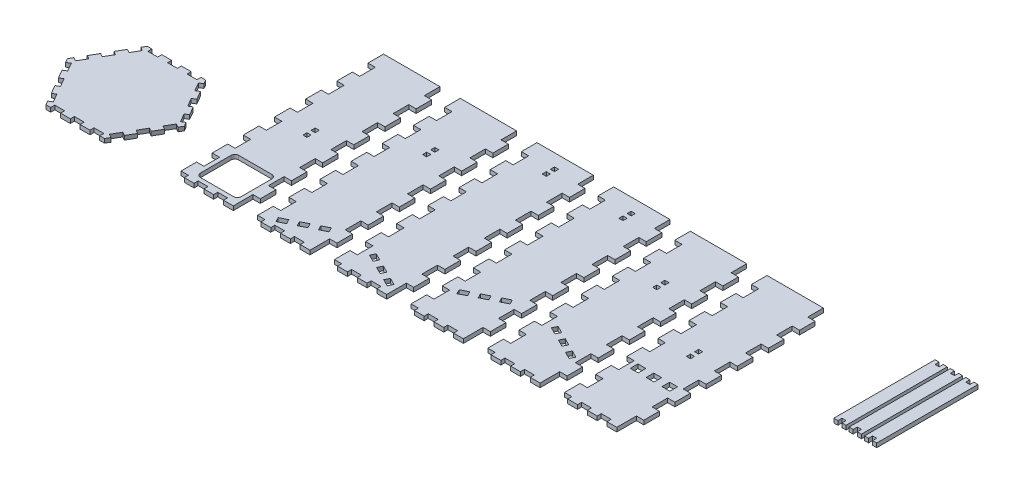
SolidWorks part; units mm, degrees
ref_plane "Front Plane" through (0, 0, 0) normal (0, 0, 1) x (1, 0, 0)
ref_plane "Top Plane" through (0, 0, 0) normal (0, 1, 0) x (1, 0, 0)
ref_plane "Right Plane" through (0, 0, 0) normal (1, 0, 0) x (0, 0, -1)
sketch "Sketch1" plane through (0, 0, 0) normal (0, 1, 0) x (1, 0, 0)
  line L0 (-22.87, -39.612) -> (-19.175, -39.612)
  line L13 (-19.175, -39.612) -> (-19.175, -36.412)
  line L14 (-19.175, -36.412) -> (-11.505, -36.412)
  line L15 (-11.505, -36.412) -> (-11.505, -39.612)
  line L16 (-11.505, -39.612) -> (-3.835, -39.612)
  line L17 (-3.835, -39.612) -> (-3.835, -36.412)
  line L18 (-3.835, -36.412) -> (3.835, -36.412)
  line L19 (3.835, -36.412) -> (3.835, -39.612)
  line L21 (-45.74, 0) -> (-43.8925, -3.2)
  line L22 (3.835, -39.612) -> (11.505, -39.612)
  line L23 (11.505, -39.612) -> (11.505, -36.412)
  line L24 (11.505, -36.412) -> (19.175, -36.412)
  line L25 (19.175, -36.412) -> (19.175, -39.612)
  line L26 (19.175, -39.612) -> (22.87, -39.612)
  line L27 (22.87, -39.612) -> (24.7175, -36.412)
  line L28 (45.74, 0) -> (22.87, 39.612) construction
  line L29 (24.7175, -36.412) -> (21.9462, -34.812)
  line L30 (21.9462, -34.812) -> (25.7812, -28.1696)
  line L31 (25.7812, -28.1696) -> (28.5525, -29.7696)
  line L32 (28.5525, -29.7696) -> (32.3875, -23.1272)
  line L33 (32.3875, -23.1272) -> (29.6162, -21.5272)
  line L34 (29.6162, -21.5272) -> (33.4512, -14.8848)
  line L35 (33.4512, -14.8848) -> (36.2225, -16.4848)
  line L36 (36.2225, -16.4848) -> (40.0575, -9.8424)
  line L37 (40.0575, -9.8424) -> (37.2862, -8.2424)
  line L38 (37.2862, -8.2424) -> (41.1212, -1.6)
  line L39 (41.1212, -1.6) -> (43.8925, -3.2)
  line L40 (43.8925, -3.2) -> (45.74, 0)
  line L41 (45.74, 0) -> (43.8925, 3.2)
  line L42 (22.87, 39.612) -> (-22.87, 39.612) construction
  line L43 (-22.87, 39.612) -> (-45.74, 0) construction
  line L44 (43.8925, 3.2) -> (41.1212, 1.6)
  line L45 (41.1212, 1.6) -> (37.2862, 8.2424)
  line L46 (37.2862, 8.2424) -> (40.0575, 9.8424)
  line L47 (40.0575, 9.8424) -> (36.2225, 16.4848)
  line L48 (36.2225, 16.4848) -> (33.4512, 14.8848)
  line L49 (33.4512, 14.8848) -> (29.6162, 21.5272)
  line L50 (29.6162, 21.5272) -> (32.3875, 23.1272)
  line L51 (32.3875, 23.1272) -> (28.5525, 29.7696)
  line L52 (28.5525, 29.7696) -> (25.7812, 28.1696)
  line L53 (25.7812, 28.1696) -> (21.9462, 34.812)
  line L54 (21.9462, 34.812) -> (24.7175, 36.412)
  line L55 (24.7175, 36.412) -> (22.87, 39.612)
  line L56 (22.87, 39.612) -> (19.175, 39.612)
  line L57 (-45.74, 0) -> (-22.87, -39.612) construction
  line L58 (-22.87, -39.612) -> (22.87, -39.612) construction
  line L59 (19.175, 39.612) -> (19.175, 36.412)
  line L60 (19.175, 36.412) -> (11.505, 36.412)
  line L61 (11.505, 36.412) -> (11.505, 39.612)
  line L62 (11.505, 39.612) -> (3.835, 39.612)
  line L63 (3.835, 39.612) -> (3.835, 36.412)
  line L64 (3.835, 36.412) -> (-3.835, 36.412)
  line L65 (-3.835, 36.412) -> (-3.835, 39.612)
  line L66 (-3.835, 39.612) -> (-11.505, 39.612)
  line L67 (-11.505, 39.612) -> (-11.505, 36.412)
  line L68 (-11.505, 36.412) -> (-19.175, 36.412)
  line L69 (-19.175, 36.412) -> (-19.175, 39.612)
  line L70 (-19.175, 39.612) -> (-22.87, 39.612)
  line L71 (-22.87, 39.612) -> (-24.7175, 36.412)
  line L72 (22.87, -39.612) -> (45.74, 0) construction
  line L73 (-43.8925, -3.2) -> (-41.1212, -1.6)
  line L74 (-24.7175, 36.412) -> (-21.9462, 34.812)
  line L75 (-21.9462, 34.812) -> (-25.7812, 28.1696)
  line L76 (-25.7812, 28.1696) -> (-28.5525, 29.7696)
  line L77 (-28.5525, 29.7696) -> (-32.3875, 23.1272)
  line L78 (-32.3875, 23.1272) -> (-29.6162, 21.5272)
  line L79 (-29.6162, 21.5272) -> (-33.4512, 14.8848)
  line L80 (-33.4512, 14.8848) -> (-36.2225, 16.4848)
  line L81 (-36.2225, 16.4848) -> (-40.0575, 9.8424)
  line L82 (-40.0575, 9.8424) -> (-37.2862, 8.2424)
  line L83 (-37.2862, 8.2424) -> (-41.1212, 1.6)
  line L84 (-41.1212, 1.6) -> (-43.8925, 3.2)
  line L85 (-43.8925, 3.2) -> (-45.74, 0)
  line L86 (-41.1212, -1.6) -> (-37.2862, -8.2424)
  line L87 (-37.2862, -8.2424) -> (-40.0575, -9.8424)
  line L88 (-40.0575, -9.8424) -> (-36.2225, -16.4848)
  line L89 (-36.2225, -16.4848) -> (-33.4512, -14.8848)
  line L90 (-33.4512, -14.8848) -> (-29.6162, -21.5272)
  line L91 (-29.6162, -21.5272) -> (-32.3875, -23.1272)
  line L92 (-32.3875, -23.1272) -> (-28.5525, -29.7696)
  line L93 (-28.5525, -29.7696) -> (-25.7812, -28.1696)
  line L94 (-25.7812, -28.1696) -> (-21.9462, -34.812)
  line L95 (-21.9462, -34.812) -> (-24.7175, -36.412)
  line L96 (-24.7175, -36.412) -> (-22.87, -39.612)
  line L97 (-21.9462, -34.812) -> (-19.175, -39.612) construction
  line L102 (19.175, -36.412) -> (24.7175, -36.412) construction
  line L103 (-19.175, -36.412) -> (-24.7175, -36.412) construction
  line L104 (80.5528, -34.8794) -> (88.2227, -34.8794)
  line L105 (88.2227, -34.8794) -> (88.2227, -31.6794)
  line L106 (88.2227, -31.6794) -> (95.8927, -31.6794)
  line L107 (95.8927, -31.6794) -> (95.8927, -34.8794)
  line L108 (95.8927, -34.8794) -> (103.5627, -34.8794)
  line L109 (103.5627, -34.8794) -> (103.5627, -31.6794)
  line L110 (103.5627, -31.6794) -> (111.2327, -31.6794)
  line L111 (111.2327, -31.6794) -> (111.2327, -34.8794)
  line L112 (111.2327, -34.8794) -> (118.9027, -34.8794)
  line L113 (80.5528, -34.8794) -> (80.5528, -31.6794)
  line L114 (80.5528, -31.6794) -> (74.8102, -31.6794)
  line L115 (74.8102, -31.6794) -> (74.8102, -19.4911)
  line L116 (74.8102, -19.4911) -> (80.5528, -19.4911)
  line L117 (80.5528, -19.4911) -> (80.5528, -7.3028)
  line L118 (80.5528, -7.3028) -> (74.8102, -7.3028)
  line L121 (118.9027, -7.3028) -> (124.6452, -7.3028)
  line L122 (124.6452, -7.3028) -> (124.6452, -19.4911)
  line L123 (124.6452, -19.4911) -> (118.9027, -19.4911)
  line L124 (118.9027, -19.4911) -> (118.9027, -34.8794)
  line L126 (21.9462, -34.812) -> (19.175, -39.612) construction
  line L250 (140.5528, -34.8794) -> (148.2227, -34.8794)
  line L265 (148.2227, -34.8794) -> (148.2227, -31.6794)
  line L266 (148.2227, -31.6794) -> (155.8927, -31.6794)
  line L267 (155.8927, -31.6794) -> (155.8927, -34.8794)
  line L268 (155.8927, -34.8794) -> (163.5627, -34.8794)
  line L269 (163.5627, -34.8794) -> (163.5627, -31.6794)
  line L270 (74.8102, -7.3028) -> (74.8102, 4.8855)
  line L271 (74.8102, 4.8855) -> (80.5528, 4.8855)
  line L272 (80.5528, 4.8855) -> (80.5528, 17.0739)
  line L273 (80.5528, 17.0739) -> (74.8102, 17.0739)
  line L274 (74.8102, 17.0739) -> (74.8102, 29.2622)
  line L275 (74.8102, 29.2622) -> (80.5528, 29.2622)
  line L276 (80.5528, 29.2622) -> (80.5528, 41.4505)
  line L277 (80.5528, 41.4505) -> (74.8102, 41.4505)
  line L278 (74.8102, 41.4505) -> (74.8102, 53.6388)
  line L279 (74.8102, 53.6388) -> (80.5528, 53.6388)
  line L280 (80.5528, 53.6388) -> (80.5528, 65.8271)
  line L281 (80.5528, 65.8271) -> (74.8102, 65.8271)
  line L282 (74.8102, 65.8271) -> (74.8102, 78.0154)
  line L283 (74.8102, 78.0154) -> (80.5528, 78.0154)
  line L284 (80.5528, 78.0154) -> (80.5528, 90.2037)
  line L285 (80.5528, 90.2037) -> (74.8102, 90.2037)
  line L286 (74.8102, 90.2037) -> (74.8102, 102.392)
  line L287 (74.8102, 102.392) -> (80.5528, 102.392)
  line L288 (80.5528, 102.392) -> (80.5528, 114.5803)
  line L289 (80.5528, 114.5803) -> (74.8102, 114.5803)
  line L290 (74.8102, 114.5803) -> (74.8102, 126.7686)
  line L291 (118.9027, -7.3028) -> (118.9027, 4.8855)
  line L292 (118.9027, 4.8855) -> (124.6452, 4.8855)
  line L293 (124.6452, 4.8855) -> (124.6452, 17.0739)
  line L294 (124.6452, 17.0739) -> (118.9027, 17.0739)
  line L295 (118.9027, 17.0739) -> (118.9027, 29.2622)
  line L296 (118.9027, 29.2622) -> (124.6452, 29.2622)
  line L297 (124.6452, 29.2622) -> (124.6452, 41.4505)
  line L298 (124.6452, 41.4505) -> (118.9027, 41.4505)
  line L299 (118.9027, 41.4505) -> (118.9027, 53.6388)
  line L300 (118.9027, 53.6388) -> (124.6452, 53.6388)
  line L301 (124.6452, 53.6388) -> (124.6452, 65.8271)
  line L302 (124.6452, 65.8271) -> (118.9027, 65.8271)
  line L303 (118.9027, 65.8271) -> (118.9027, 78.0154)
  line L304 (118.9027, 78.0154) -> (124.6452, 78.0154)
  line L305 (124.6452, 78.0154) -> (124.6452, 90.2037)
  line L306 (124.6452, 90.2037) -> (118.9027, 90.2037)
  line L307 (118.9027, 90.2037) -> (118.9027, 102.392)
  line L308 (118.9027, 102.392) -> (124.6452, 102.392)
  line L309 (124.6452, 102.392) -> (124.6452, 114.5803)
  line L310 (124.6452, 114.5803) -> (118.9027, 114.5803)
  line L311 (118.9027, 114.5803) -> (118.9027, 126.7686)
  line L312 (163.5627, -31.6794) -> (171.2327, -31.6794)
  line L313 (171.2327, -31.6794) -> (171.2327, -34.8794)
  line L314 (171.2327, -34.8794) -> (178.9027, -34.8794)
  line L315 (140.5528, -34.8794) -> (140.5528, -31.6794)
  line L316 (140.5528, -31.6794) -> (134.8102, -31.6794)
  line L317 (134.8102, -31.6794) -> (134.8102, -19.4911)
  line L318 (134.8102, -19.4911) -> (140.5528, -19.4911)
  line L319 (140.5528, -19.4911) -> (140.5528, -7.3028)
  line L320 (140.5528, -7.3028) -> (134.8102, -7.3028)
  line L322 (178.9027, -7.3028) -> (184.6452, -7.3028)
  line L323 (184.6452, -7.3028) -> (184.6452, -19.4911)
  line L324 (184.6452, -19.4911) -> (178.9027, -19.4911)
  line L325 (178.9027, -19.4911) -> (178.9027, -34.8794)
  line L326 (134.8102, -7.3028) -> (134.8102, 4.8855)
  line L327 (134.8102, 4.8855) -> (140.5528, 4.8855)
  line L328 (140.5528, 4.8855) -> (140.5528, 17.0739)
  line L329 (140.5528, 17.0739) -> (134.8102, 17.0739)
  line L330 (134.8102, 17.0739) -> (134.8102, 29.2622)
  line L331 (134.8102, 29.2622) -> (140.5528, 29.2622)
  line L332 (140.5528, 29.2622) -> (140.5528, 41.4505)
  line L333 (140.5528, 41.4505) -> (134.8102, 41.4505)
  line L334 (134.8102, 41.4505) -> (134.8102, 53.6388)
  line L335 (134.8102, 53.6388) -> (140.5528, 53.6388)
  line L336 (140.5528, 53.6388) -> (140.5528, 65.8271)
  line L337 (140.5528, 65.8271) -> (134.8102, 65.8271)
  line L338 (134.8102, 65.8271) -> (134.8102, 78.0154)
  line L339 (134.8102, 78.0154) -> (140.5528, 78.0154)
  line L340 (140.5528, 78.0154) -> (140.5528, 90.2037)
  line L341 (140.5528, 90.2037) -> (134.8102, 90.2037)
  line L342 (134.8102, 90.2037) -> (134.8102, 102.392)
  line L343 (134.8102, 102.392) -> (140.5528, 102.392)
  line L344 (140.5528, 102.392) -> (140.5528, 114.5803)
  line L345 (140.5528, 114.5803) -> (134.8102, 114.5803)
  line L346 (134.8102, 114.5803) -> (134.8102, 126.7686)
  line L347 (178.9027, -7.3028) -> (178.9027, 4.8855)
  line L348 (178.9027, 4.8855) -> (184.6452, 4.8855)
  line L349 (184.6452, 4.8855) -> (184.6452, 17.0739)
  line L350 (184.6452, 17.0739) -> (178.9027, 17.0739)
  line L351 (178.9027, 17.0739) -> (178.9027, 29.2622)
  line L352 (178.9027, 29.2622) -> (184.6452, 29.2622)
  line L353 (184.6452, 29.2622) -> (184.6452, 41.4505)
  line L354 (184.6452, 41.4505) -> (178.9027, 41.4505)
  line L355 (178.9027, 41.4505) -> (178.9027, 53.6388)
  line L356 (178.9027, 53.6388) -> (184.6452, 53.6388)
  line L357 (184.6452, 53.6388) -> (184.6452, 65.8271)
  line L358 (184.6452, 65.8271) -> (178.9027, 65.8271)
  line L359 (178.9027, 65.8271) -> (178.9027, 78.0154)
  line L360 (178.9027, 78.0154) -> (184.6452, 78.0154)
  line L361 (184.6452, 78.0154) -> (184.6452, 90.2037)
  line L362 (184.6452, 90.2037) -> (178.9027, 90.2037)
  line L363 (178.9027, 90.2037) -> (178.9027, 102.392)
  line L364 (178.9027, 102.392) -> (184.6452, 102.392)
  line L365 (184.6452, 102.392) -> (184.6452, 114.5803)
  line L366 (184.6452, 114.5803) -> (178.9027, 114.5803)
  line L367 (178.9027, 114.5803) -> (178.9027, 126.7686)
  line L369 (200.5528, -34.8794) -> (208.2227, -34.8794)
  line L370 (208.2227, -34.8794) -> (208.2227, -31.6794)
  line L371 (208.2227, -31.6794) -> (215.8927, -31.6794)
  line L372 (215.8927, -31.6794) -> (215.8927, -34.8794)
  line L373 (215.8927, -34.8794) -> (223.5627, -34.8794)
  line L374 (223.5627, -34.8794) -> (223.5627, -31.6794)
  line L375 (223.5627, -31.6794) -> (231.2327, -31.6794)
  line L376 (231.2327, -31.6794) -> (231.2327, -34.8794)
  line L377 (231.2327, -34.8794) -> (238.9027, -34.8794)
  line L378 (200.5528, -34.8794) -> (200.5528, -31.6794)
  line L379 (200.5528, -31.6794) -> (194.8102, -31.6794)
  line L380 (194.8102, -31.6794) -> (194.8102, -19.4911)
  line L381 (194.8102, -19.4911) -> (200.5528, -19.4911)
  line L382 (200.5528, -19.4911) -> (200.5528, -7.3028)
  line L383 (200.5528, -7.3028) -> (194.8102, -7.3028)
  line L385 (238.9027, -7.3028) -> (244.6452, -7.3028)
  line L386 (244.6452, -7.3028) -> (244.6452, -19.4911)
  line L387 (244.6452, -19.4911) -> (238.9027, -19.4911)
  line L388 (238.9027, -19.4911) -> (238.9027, -34.8794)
  line L389 (194.8102, -7.3028) -> (194.8102, 4.8855)
  line L390 (194.8102, 4.8855) -> (200.5528, 4.8855)
  line L391 (200.5528, 4.8855) -> (200.5528, 17.0739)
  line L392 (200.5528, 17.0739) -> (194.8102, 17.0739)
  line L393 (194.8102, 17.0739) -> (194.8102, 29.2622)
  line L394 (194.8102, 29.2622) -> (200.5528, 29.2622)
  line L395 (200.5528, 29.2622) -> (200.5528, 41.4505)
  line L396 (200.5528, 41.4505) -> (194.8102, 41.4505)
  line L397 (194.8102, 41.4505) -> (194.8102, 53.6388)
  line L398 (194.8102, 53.6388) -> (200.5528, 53.6388)
  line L399 (200.5528, 53.6388) -> (200.5528, 65.8271)
  line L400 (200.5528, 65.8271) -> (194.8102, 65.8271)
  line L401 (194.8102, 65.8271) -> (194.8102, 78.0154)
  line L402 (194.8102, 78.0154) -> (200.5528, 78.0154)
  line L403 (200.5528, 78.0154) -> (200.5528, 90.2037)
  line L404 (200.5528, 90.2037) -> (194.8102, 90.2037)
  line L405 (194.8102, 90.2037) -> (194.8102, 102.392)
  line L406 (194.8102, 102.392) -> (200.5528, 102.392)
  line L407 (200.5528, 102.392) -> (200.5528, 114.5803)
  line L408 (200.5528, 114.5803) -> (194.8102, 114.5803)
  line L409 (194.8102, 114.5803) -> (194.8102, 126.7686)
  line L410 (238.9027, -7.3028) -> (238.9027, 4.8855)
  line L411 (238.9027, 4.8855) -> (244.6452, 4.8855)
  line L412 (244.6452, 4.8855) -> (244.6452, 17.0739)
  line L413 (244.6452, 17.0739) -> (238.9027, 17.0739)
  line L414 (238.9027, 17.0739) -> (238.9027, 29.2622)
  line L415 (238.9027, 29.2622) -> (244.6452, 29.2622)
  line L416 (244.6452, 29.2622) -> (244.6452, 41.4505)
  line L417 (244.6452, 41.4505) -> (238.9027, 41.4505)
  line L418 (238.9027, 41.4505) -> (238.9027, 53.6388)
  line L419 (238.9027, 53.6388) -> (244.6452, 53.6388)
  line L420 (244.6452, 53.6388) -> (244.6452, 65.8271)
  line L421 (244.6452, 65.8271) -> (238.9027, 65.8271)
  line L422 (238.9027, 65.8271) -> (238.9027, 78.0154)
  line L423 (238.9027, 78.0154) -> (244.6452, 78.0154)
  line L424 (244.6452, 78.0154) -> (244.6452, 90.2037)
  line L425 (244.6452, 90.2037) -> (238.9027, 90.2037)
  line L426 (238.9027, 90.2037) -> (238.9027, 102.392)
  line L427 (238.9027, 102.392) -> (244.6452, 102.392)
  line L428 (244.6452, 102.392) -> (244.6452, 114.5803)
  line L429 (244.6452, 114.5803) -> (238.9027, 114.5803)
  line L430 (238.9027, 114.5803) -> (238.9027, 126.7686)
  line L432 (260.5528, -34.8794) -> (268.2227, -34.8794)
  line L433 (268.2227, -34.8794) -> (268.2227, -31.6794)
  line L434 (268.2227, -31.6794) -> (275.8927, -31.6794)
  line L435 (275.8927, -31.6794) -> (275.8927, -34.8794)
  line L436 (275.8927, -34.8794) -> (283.5627, -34.8794)
  line L437 (283.5627, -34.8794) -> (283.5627, -31.6794)
  line L438 (283.5627, -31.6794) -> (291.2327, -31.6794)
  line L439 (291.2327, -31.6794) -> (291.2327, -34.8794)
  line L440 (291.2327, -34.8794) -> (298.9027, -34.8794)
  line L441 (260.5528, -34.8794) -> (260.5528, -31.6794)
  line L442 (260.5528, -31.6794) -> (254.8102, -31.6794)
  line L443 (254.8102, -31.6794) -> (254.8102, -19.4911)
  line L444 (254.8102, -19.4911) -> (260.5528, -19.4911)
  line L445 (260.5528, -19.4911) -> (260.5528, -7.3028)
  line L446 (260.5528, -7.3028) -> (254.8102, -7.3028)
  line L448 (298.9027, -7.3028) -> (304.6452, -7.3028)
  line L449 (304.6452, -7.3028) -> (304.6452, -19.4911)
  line L450 (304.6452, -19.4911) -> (298.9027, -19.4911)
  line L451 (298.9027, -19.4911) -> (298.9027, -34.8794)
  line L452 (254.8102, -7.3028) -> (254.8102, 4.8855)
  line L453 (254.8102, 4.8855) -> (260.5528, 4.8855)
  line L454 (260.5528, 4.8855) -> (260.5528, 17.0739)
  line L455 (260.5528, 17.0739) -> (254.8102, 17.0739)
  line L456 (254.8102, 17.0739) -> (254.8102, 29.2622)
  line L457 (254.8102, 29.2622) -> (260.5528, 29.2622)
  line L458 (260.5528, 29.2622) -> (260.5528, 41.4505)
  line L459 (260.5528, 41.4505) -> (254.8102, 41.4505)
  line L460 (254.8102, 41.4505) -> (254.8102, 53.6388)
  line L461 (254.8102, 53.6388) -> (260.5528, 53.6388)
  line L462 (260.5528, 53.6388) -> (260.5528, 65.8271)
  line L463 (260.5528, 65.8271) -> (254.8102, 65.8271)
  line L464 (254.8102, 65.8271) -> (254.8102, 78.0154)
  line L465 (254.8102, 78.0154) -> (260.5528, 78.0154)
  line L466 (260.5528, 78.0154) -> (260.5528, 90.2037)
  line L467 (260.5528, 90.2037) -> (254.8102, 90.2037)
  line L468 (254.8102, 90.2037) -> (254.8102, 102.392)
  line L469 (254.8102, 102.392) -> (260.5528, 102.392)
  line L470 (260.5528, 102.392) -> (260.5528, 114.5803)
  line L471 (260.5528, 114.5803) -> (254.8102, 114.5803)
  line L472 (254.8102, 114.5803) -> (254.8102, 126.7686)
  line L473 (298.9027, -7.3028) -> (298.9027, 4.8855)
  line L474 (298.9027, 4.8855) -> (304.6452, 4.8855)
  line L475 (304.6452, 4.8855) -> (304.6452, 17.0739)
  line L476 (304.6452, 17.0739) -> (298.9027, 17.0739)
  line L477 (298.9027, 17.0739) -> (298.9027, 29.2622)
  line L478 (298.9027, 29.2622) -> (304.6452, 29.2622)
  line L479 (304.6452, 29.2622) -> (304.6452, 41.4505)
  line L480 (304.6452, 41.4505) -> (298.9027, 41.4505)
  line L481 (298.9027, 41.4505) -> (298.9027, 53.6388)
  line L482 (298.9027, 53.6388) -> (304.6452, 53.6388)
  line L483 (304.6452, 53.6388) -> (304.6452, 65.8271)
  line L484 (304.6452, 65.8271) -> (298.9027, 65.8271)
  line L485 (298.9027, 65.8271) -> (298.9027, 78.0154)
  line L486 (298.9027, 78.0154) -> (304.6452, 78.0154)
  line L487 (304.6452, 78.0154) -> (304.6452, 90.2037)
  line L488 (304.6452, 90.2037) -> (298.9027, 90.2037)
  line L489 (298.9027, 90.2037) -> (298.9027, 102.392)
  line L490 (298.9027, 102.392) -> (304.6452, 102.392)
  line L491 (304.6452, 102.392) -> (304.6452, 114.5803)
  line L492 (304.6452, 114.5803) -> (298.9027, 114.5803)
  line L493 (298.9027, 114.5803) -> (298.9027, 126.7686)
  line L495 (320.5528, -34.8794) -> (328.2227, -34.8794)
  line L496 (328.2227, -34.8794) -> (328.2227, -31.6794)
  line L497 (328.2227, -31.6794) -> (335.8927, -31.6794)
  line L498 (335.8927, -31.6794) -> (335.8927, -34.8794)
  line L499 (335.8927, -34.8794) -> (343.5627, -34.8794)
  line L500 (343.5627, -34.8794) -> (343.5627, -31.6794)
  line L501 (343.5627, -31.6794) -> (351.2327, -31.6794)
  line L502 (351.2327, -31.6794) -> (351.2327, -34.8794)
  line L503 (351.2327, -34.8794) -> (358.9027, -34.8794)
  line L504 (320.5528, -34.8794) -> (320.5528, -31.6794)
  line L505 (320.5528, -31.6794) -> (314.8102, -31.6794)
  line L506 (314.8102, -31.6794) -> (314.8102, -19.4911)
  line L507 (314.8102, -19.4911) -> (320.5528, -19.4911)
  line L508 (320.5528, -19.4911) -> (320.5528, -7.3028)
  line L509 (320.5528, -7.3028) -> (314.8102, -7.3028)
  line L511 (358.9027, -7.3028) -> (364.6452, -7.3028)
  line L512 (364.6452, -7.3028) -> (364.6452, -19.4911)
  line L513 (364.6452, -19.4911) -> (358.9027, -19.4911)
  line L514 (358.9027, -19.4911) -> (358.9027, -34.8794)
  line L515 (314.8102, -7.3028) -> (314.8102, 4.8855)
  line L516 (314.8102, 4.8855) -> (320.5528, 4.8855)
  line L517 (320.5528, 4.8855) -> (320.5528, 17.0739)
  line L518 (320.5528, 17.0739) -> (314.8102, 17.0739)
  line L519 (314.8102, 17.0739) -> (314.8102, 29.2622)
  line L520 (314.8102, 29.2622) -> (320.5528, 29.2622)
  line L521 (320.5528, 29.2622) -> (320.5528, 41.4505)
  line L522 (320.5528, 41.4505) -> (314.8102, 41.4505)
  line L523 (314.8102, 41.4505) -> (314.8102, 53.6388)
  line L524 (314.8102, 53.6388) -> (320.5528, 53.6388)
  line L525 (320.5528, 53.6388) -> (320.5528, 65.8271)
  line L526 (320.5528, 65.8271) -> (314.8102, 65.8271)
  line L527 (314.8102, 65.8271) -> (314.8102, 78.0154)
  line L528 (314.8102, 78.0154) -> (320.5528, 78.0154)
  line L529 (320.5528, 78.0154) -> (320.5528, 90.2037)
  line L530 (320.5528, 90.2037) -> (314.8102, 90.2037)
  line L531 (314.8102, 90.2037) -> (314.8102, 102.392)
  line L532 (314.8102, 102.392) -> (320.5528, 102.392)
  line L533 (320.5528, 102.392) -> (320.5528, 114.5803)
  line L534 (320.5528, 114.5803) -> (314.8102, 114.5803)
  line L535 (314.8102, 114.5803) -> (314.8102, 126.7686)
  line L536 (358.9027, -7.3028) -> (358.9027, 4.8855)
  line L537 (358.9027, 4.8855) -> (364.6452, 4.8855)
  line L538 (364.6452, 4.8855) -> (364.6452, 17.0739)
  line L539 (364.6452, 17.0739) -> (358.9027, 17.0739)
  line L540 (358.9027, 17.0739) -> (358.9027, 29.2622)
  line L541 (358.9027, 29.2622) -> (364.6452, 29.2622)
  line L542 (364.6452, 29.2622) -> (364.6452, 41.4505)
  line L543 (364.6452, 41.4505) -> (358.9027, 41.4505)
  line L544 (358.9027, 41.4505) -> (358.9027, 53.6388)
  line L545 (358.9027, 53.6388) -> (364.6452, 53.6388)
  line L546 (364.6452, 53.6388) -> (364.6452, 65.8271)
  line L547 (364.6452, 65.8271) -> (358.9027, 65.8271)
  line L548 (358.9027, 65.8271) -> (358.9027, 78.0154)
  line L549 (358.9027, 78.0154) -> (364.6452, 78.0154)
  line L550 (364.6452, 78.0154) -> (364.6452, 90.2037)
  line L551 (364.6452, 90.2037) -> (358.9027, 90.2037)
  line L552 (358.9027, 90.2037) -> (358.9027, 102.392)
  line L553 (358.9027, 102.392) -> (364.6452, 102.392)
  line L554 (364.6452, 102.392) -> (364.6452, 114.5803)
  line L555 (364.6452, 114.5803) -> (358.9027, 114.5803)
  line L556 (358.9027, 114.5803) -> (358.9027, 126.7686)
  line L558 (380.5528, -34.8794) -> (388.2227, -34.8794)
  line L559 (388.2227, -34.8794) -> (388.2227, -31.6794)
  line L560 (388.2227, -31.6794) -> (395.8927, -31.6794)
  line L561 (395.8927, -31.6794) -> (395.8927, -34.8794)
  line L562 (395.8927, -34.8794) -> (403.5627, -34.8794)
  line L563 (403.5627, -34.8794) -> (403.5627, -31.6794)
  line L564 (403.5627, -31.6794) -> (411.2327, -31.6794)
  line L565 (411.2327, -31.6794) -> (411.2327, -34.8794)
  line L566 (411.2327, -34.8794) -> (418.9027, -34.8794)
  line L567 (380.5528, -34.8794) -> (380.5528, -31.6794)
  line L568 (380.5528, -31.6794) -> (374.8102, -31.6794)
  line L569 (374.8102, -31.6794) -> (374.8102, -19.4911)
  line L570 (374.8102, -19.4911) -> (380.5528, -19.4911)
  line L571 (380.5528, -19.4911) -> (380.5528, -7.3028)
  line L572 (380.5528, -7.3028) -> (374.8102, -7.3028)
  line L574 (418.9027, -7.3028) -> (424.6452, -7.3028)
  line L575 (424.6452, -7.3028) -> (424.6452, -19.4911)
  line L576 (424.6452, -19.4911) -> (418.9027, -19.4911)
  line L577 (418.9027, -19.4911) -> (418.9027, -34.8794)
  line L578 (374.8102, -7.3028) -> (374.8102, 4.8855)
  line L579 (374.8102, 4.8855) -> (380.5528, 4.8855)
  line L580 (380.5528, 4.8855) -> (380.5528, 17.0739)
  line L581 (380.5528, 17.0739) -> (374.8102, 17.0739)
  line L582 (374.8102, 17.0739) -> (374.8102, 29.2622)
  line L583 (374.8102, 29.2622) -> (380.5528, 29.2622)
  line L584 (380.5528, 29.2622) -> (380.5528, 41.4505)
  line L585 (380.5528, 41.4505) -> (374.8102, 41.4505)
  line L586 (374.8102, 41.4505) -> (374.8102, 53.6388)
  line L587 (374.8102, 53.6388) -> (380.5528, 53.6388)
  line L588 (380.5528, 53.6388) -> (380.5528, 65.8271)
  line L589 (380.5528, 65.8271) -> (374.8102, 65.8271)
  line L590 (374.8102, 65.8271) -> (374.8102, 78.0154)
  line L591 (374.8102, 78.0154) -> (380.5528, 78.0154)
  line L592 (380.5528, 78.0154) -> (380.5528, 90.2037)
  line L593 (380.5528, 90.2037) -> (374.8102, 90.2037)
  line L594 (374.8102, 90.2037) -> (374.8102, 102.392)
  line L595 (374.8102, 102.392) -> (380.5528, 102.392)
  line L596 (380.5528, 102.392) -> (380.5528, 114.5803)
  line L597 (380.5528, 114.5803) -> (374.8102, 114.5803)
  line L598 (374.8102, 114.5803) -> (374.8102, 126.7686)
  line L599 (418.9027, -7.3028) -> (418.9027, 4.8855)
  line L600 (418.9027, 4.8855) -> (424.6452, 4.8855)
  line L601 (424.6452, 4.8855) -> (424.6452, 17.0739)
  line L602 (424.6452, 17.0739) -> (418.9027, 17.0739)
  line L603 (418.9027, 17.0739) -> (418.9027, 29.2622)
  line L604 (418.9027, 29.2622) -> (424.6452, 29.2622)
  line L605 (424.6452, 29.2622) -> (424.6452, 41.4505)
  line L606 (424.6452, 41.4505) -> (418.9027, 41.4505)
  line L607 (418.9027, 41.4505) -> (418.9027, 53.6388)
  line L608 (418.9027, 53.6388) -> (424.6452, 53.6388)
  line L609 (424.6452, 53.6388) -> (424.6452, 65.8271)
  line L610 (424.6452, 65.8271) -> (418.9027, 65.8271)
  line L611 (418.9027, 65.8271) -> (418.9027, 78.0154)
  line L612 (418.9027, 78.0154) -> (424.6452, 78.0154)
  line L613 (424.6452, 78.0154) -> (424.6452, 90.2037)
  line L614 (424.6452, 90.2037) -> (418.9027, 90.2037)
  line L615 (418.9027, 90.2037) -> (418.9027, 102.392)
  line L616 (418.9027, 102.392) -> (424.6452, 102.392)
  line L617 (424.6452, 102.392) -> (424.6452, 114.5803)
  line L618 (424.6452, 114.5803) -> (418.9027, 114.5803)
  line L619 (418.9027, 114.5803) -> (418.9027, 126.7686)
  line L621 (144.4326, -25.24) -> (149.9783, -22.4678)
  line L622 (144.4326, -25.24) -> (146.2212, -28.8179)
  line L623 (146.2212, -28.8179) -> (151.7669, -26.0457)
  line L624 (149.9783, -22.4678) -> (151.7669, -26.0457)
  line L625 (155.524, -19.6956) -> (161.0697, -16.9234)
  line L626 (155.524, -19.6956) -> (157.3126, -23.2735)
  line L627 (157.3126, -23.2735) -> (162.8583, -20.5012)
  line L628 (161.0697, -16.9234) -> (162.8583, -20.5012)
  line L632 (166.6154, -14.1512) -> (172.1611, -11.3789)
  line L633 (166.6154, -14.1512) -> (168.404, -17.729)
  line L634 (168.404, -17.729) -> (173.9497, -14.9568)
  line L635 (172.1611, -11.3789) -> (173.9497, -14.9568)
  line L636 (118.9027, 126.7686) -> (74.8102, 126.7686)
  line L637 (134.8102, 126.7686) -> (178.9027, 126.7686)
  line L638 (194.8102, 126.7686) -> (238.9027, 126.7686)
  line L639 (254.8102, 126.7686) -> (298.9027, 126.7686)
  line L640 (314.8102, 126.7686) -> (358.9027, 126.7686)
  line L641 (374.8102, 126.7686) -> (418.9027, 126.7686)
  line L642 (-41.1212, -1.6) -> (-42.045, 0) construction
  line L643 (-42.045, 0) -> (-41.1212, 1.6) construction
  line L644 (41.1212, -1.6) -> (42.045, 0) construction
  line L645 (42.045, 0) -> (41.1212, 1.6) construction
  line L646 (-21.0225, -36.412) -> (-22.87, -39.612) construction
  line L647 (21.0225, -36.412) -> (22.87, -39.612) construction
  line L648 (138.7077, -31.6794) -> (145.8635, -28.1023) construction
  line L649 (173.592, -14.2412) -> (180.7477, -10.6642) construction
  line L650 (189.7277, 136.633) -> (189.7277, -43.0289) construction
  line L651 (138.7077, -34.8794) -> (180.7477, -34.8794) construction
  line L652 (207.2943, -11.3789) -> (205.5058, -14.9568)
  line L653 (211.0515, -17.729) -> (205.5058, -14.9568)
  line L654 (212.84, -14.1512) -> (211.0515, -17.729)
  line L655 (212.84, -14.1512) -> (207.2943, -11.3789)
  line L656 (218.3857, -16.9234) -> (216.5972, -20.5012)
  line L657 (222.1429, -23.2735) -> (216.5972, -20.5012)
  line L658 (223.9314, -19.6956) -> (222.1429, -23.2735)
  line L659 (223.9314, -19.6956) -> (218.3857, -16.9234)
  line L660 (229.4771, -22.4678) -> (227.6886, -26.0457)
  line L661 (233.2343, -28.8179) -> (227.6886, -26.0457)
  line L662 (235.0228, -25.24) -> (233.2343, -28.8179)
  line L663 (235.0228, -25.24) -> (229.4771, -22.4678)
  line L664 (252.6938, -10.4795) -> (309.7277, -10.4795) construction
  line L665 (258.7077, -34.8794) -> (300.7477, -34.8794) construction
  line L666 (258.7077, -10.4795) -> (265.8635, -6.9025) construction
  line L667 (265.8635, -6.9025) -> (264.0749, -3.3246)
  line L668 (264.0749, -3.3246) -> (269.6206, -0.5524)
  line L669 (269.6206, -0.5524) -> (271.4092, -4.1302)
  line L670 (271.4092, -4.1302) -> (265.8635, -6.9025)
  line L671 (275.1663, 2.2199) -> (276.9549, -1.358)
  line L672 (276.9549, -1.358) -> (282.5006, 1.4142)
  line L673 (282.5006, 1.4142) -> (280.712, 4.9921)
  line L674 (280.712, 4.9921) -> (275.1663, 2.2199)
  line L675 (286.2577, 7.7643) -> (288.0463, 4.1864)
  line L676 (288.0463, 4.1864) -> (293.592, 6.9586)
  line L677 (293.592, 6.9586) -> (291.8034, 10.5365)
  line L678 (291.8034, 10.5365) -> (286.2577, 7.7643)
  line L679 (293.592, 6.9586) -> (300.7477, 10.5357) construction
  line L680 (309.7277, 136.633) -> (309.7277, -43.0289) construction
  line L681 (327.652, 10.5365) -> (333.1977, 7.7643)
  line L682 (325.8635, 6.9586) -> (327.652, 10.5365)
  line L683 (331.4092, 4.1864) -> (325.8635, 6.9586)
  line L684 (333.1977, 7.7643) -> (331.4092, 4.1864)
  line L685 (338.7434, 4.9921) -> (344.2891, 2.2199)
  line L686 (336.9549, 1.4142) -> (338.7434, 4.9921)
  line L687 (342.5006, -1.358) -> (336.9549, 1.4142)
  line L688 (344.2891, 2.2199) -> (342.5006, -1.358)
  line L689 (348.0463, -4.1302) -> (353.592, -6.9025)
  line L690 (349.8348, -0.5524) -> (348.0463, -4.1302)
  line L691 (355.3805, -3.3246) -> (349.8348, -0.5524)
  line L692 (353.592, -6.9025) -> (355.3805, -3.3246)
  line L693 (384.2277, 16.3606) -> (384.2277, 10.3606)
  line L694 (384.2277, 10.3606) -> (390.4277, 10.3606)
  line L695 (390.4277, 10.3606) -> (390.4277, 16.3606)
  line L696 (390.4277, 16.3606) -> (384.2277, 16.3606)
  line L697 (396.6277, 16.3606) -> (396.6277, 10.3606)
  line L698 (396.6277, 10.3606) -> (402.8277, 10.3606)
  line L699 (402.8277, 10.3606) -> (402.8277, 16.3606)
  line L700 (402.8277, 16.3606) -> (396.6277, 16.3606)
  line L701 (409.0277, 16.3606) -> (409.0277, 10.3606)
  line L702 (409.0277, 10.3606) -> (415.2277, 10.3606)
  line L703 (415.2277, 10.3606) -> (415.2277, 16.3606)
  line L704 (415.2277, 16.3606) -> (409.0277, 16.3606)
  line L705 (384.2277, 10.3606) -> (380.5528, 10.3606) construction
  line L706 (415.2277, 10.3606) -> (418.9027, 10.3606) construction
  line L707 (86.7528, 1.5206) -> (112.7027, 1.5206)
  line L708 (112.7027, -28.4794) -> (86.7528, -28.4794)
  line L709 (83.7528, -1.4794) -> (83.7528, -25.4794)
  line L710 (115.7027, -1.4794) -> (115.7027, -25.4794)
  line L711 (249.7277, 136.633) -> (249.7277, -43.0289) construction
  line L712 (398.1277, 49.9606) -> (401.3277, 49.9606)
  line L713 (398.1277, 49.9606) -> (398.1277, 46.7606)
  line L714 (398.1277, 46.7606) -> (401.3277, 46.7606)
  line L715 (401.3277, 49.9606) -> (401.3277, 46.7606)
  line L716 (398.1277, 43.5606) -> (401.3277, 43.5606)
  line L717 (398.1277, 43.5606) -> (398.1277, 40.3606)
  line L718 (398.1277, 40.3606) -> (401.3277, 40.3606)
  line L719 (401.3277, 43.5606) -> (401.3277, 40.3606)
  line L720 (98.1277, 43.5606) -> (98.1277, 40.3606)
  line L721 (101.3277, 40.3606) -> (98.1277, 40.3606)
  line L722 (101.3277, 43.5606) -> (101.3277, 40.3606)
  line L723 (101.3277, 43.5606) -> (98.1277, 43.5606)
  line L724 (98.1277, 49.9606) -> (98.1277, 46.7606)
  line L725 (101.3277, 46.7606) -> (98.1277, 46.7606)
  line L726 (101.3277, 49.9606) -> (101.3277, 46.7606)
  line L727 (101.3277, 49.9606) -> (98.1277, 49.9606)
  line L728 (158.1277, 77.1606) -> (158.1277, 73.9606)
  line L729 (161.3277, 73.9606) -> (158.1277, 73.9606)
  line L730 (161.3277, 77.1606) -> (161.3277, 73.9606)
  line L731 (161.3277, 77.1606) -> (158.1277, 77.1606)
  line L732 (158.1277, 83.5606) -> (158.1277, 80.3606)
  line L733 (161.3277, 80.3606) -> (158.1277, 80.3606)
  line L734 (161.3277, 83.5606) -> (161.3277, 80.3606)
  line L735 (161.3277, 83.5606) -> (158.1277, 83.5606)
  line L736 (338.1277, 83.5606) -> (341.3277, 83.5606)
  line L737 (338.1277, 83.5606) -> (338.1277, 80.3606)
  line L738 (338.1277, 80.3606) -> (341.3277, 80.3606)
  line L739 (341.3277, 83.5606) -> (341.3277, 80.3606)
  line L740 (338.1277, 77.1606) -> (341.3277, 77.1606)
  line L741 (338.1277, 77.1606) -> (338.1277, 73.9606)
  line L742 (338.1277, 73.9606) -> (341.3277, 73.9606)
  line L743 (341.3277, 77.1606) -> (341.3277, 73.9606)
  line L744 (218.1277, 110.7606) -> (218.1277, 107.5606)
  line L745 (221.3277, 107.5606) -> (218.1277, 107.5606)
  line L746 (221.3277, 110.7606) -> (221.3277, 107.5606)
  line L747 (221.3277, 110.7606) -> (218.1277, 110.7606)
  line L748 (218.1277, 117.1606) -> (218.1277, 113.9606)
  line L749 (221.3277, 113.9606) -> (218.1277, 113.9606)
  line L750 (221.3277, 117.1606) -> (221.3277, 113.9606)
  line L751 (221.3277, 117.1606) -> (218.1277, 117.1606)
  line L752 (278.1277, 117.1606) -> (281.3277, 117.1606)
  line L753 (278.1277, 117.1606) -> (278.1277, 113.9606)
  line L754 (278.1277, 113.9606) -> (281.3277, 113.9606)
  line L755 (281.3277, 117.1606) -> (281.3277, 113.9606)
  line L756 (278.1277, 110.7606) -> (281.3277, 110.7606)
  line L757 (278.1277, 110.7606) -> (278.1277, 107.5606)
  line L758 (278.1277, 107.5606) -> (281.3277, 107.5606)
  line L759 (281.3277, 110.7606) -> (281.3277, 107.5606)
  line L760 (497.6107, 135.4038) -> (497.6107, 56.1838)
  line L761 (500.8107, 56.1838) -> (500.8107, 59.3838)
  line L762 (500.8107, 59.3838) -> (504.0107, 59.3838)
  line L763 (504.0107, 59.3838) -> (504.0107, 56.1838)
  line L764 (504.0107, 56.1838) -> (507.2107, 56.1838)
  line L765 (507.2107, 56.1838) -> (507.2107, 135.4038)
  line L766 (507.2107, 135.4038) -> (504.0107, 135.4038)
  line L767 (504.0107, 135.4038) -> (504.0107, 132.2038)
  line L768 (504.0107, 132.2038) -> (500.8107, 132.2038)
  line L769 (500.8107, 132.2038) -> (500.8107, 135.4038)
  line L770 (500.8107, 135.4038) -> (497.6107, 135.4038)
  line L771 (500.8107, 56.1838) -> (497.6107, 56.1838)
  line L772 (509.6107, 135.4038) -> (509.6107, 56.1838)
  line L773 (512.8107, 56.1838) -> (512.8107, 59.3838)
  line L774 (512.8107, 59.3838) -> (516.0107, 59.3838)
  line L775 (516.0107, 59.3838) -> (516.0107, 56.1838)
  line L776 (516.0107, 56.1838) -> (519.2107, 56.1838)
  line L777 (519.2107, 56.1838) -> (519.2107, 135.4038)
  line L778 (519.2107, 135.4038) -> (516.0107, 135.4038)
  line L779 (516.0107, 135.4038) -> (516.0107, 132.2038)
  line L780 (516.0107, 132.2038) -> (512.8107, 132.2038)
  line L781 (512.8107, 132.2038) -> (512.8107, 135.4038)
  line L782 (512.8107, 135.4038) -> (509.6107, 135.4038)
  line L783 (512.8107, 56.1838) -> (509.6107, 56.1838)
  line L784 (521.6107, 135.4038) -> (521.6107, 56.1838)
  line L785 (524.8107, 56.1838) -> (524.8107, 59.3838)
  line L786 (524.8107, 59.3838) -> (528.0107, 59.3838)
  line L787 (528.0107, 59.3838) -> (528.0107, 56.1838)
  line L788 (528.0107, 56.1838) -> (531.2107, 56.1838)
  line L789 (531.2107, 56.1838) -> (531.2107, 135.4038)
  line L790 (531.2107, 135.4038) -> (528.0107, 135.4038)
  line L791 (528.0107, 135.4038) -> (528.0107, 132.2038)
  line L792 (528.0107, 132.2038) -> (524.8107, 132.2038)
  line L793 (524.8107, 132.2038) -> (524.8107, 135.4038)
  line L794 (524.8107, 135.4038) -> (521.6107, 135.4038)
  line L795 (524.8107, 56.1838) -> (521.6107, 56.1838)
  circle A0 centre (0, 0) radius 39.612 construction
  arc A5 (86.7528, -28.4794) -> (83.7528, -25.4794) centre (86.7528, -25.4794) cw
  arc A6 (83.7528, -1.4794) -> (86.7528, 1.5206) centre (86.7528, -1.4794) cw
  arc A7 (112.7027, 1.5206) -> (115.7027, -1.4794) centre (112.7027, -1.4794) cw
  arc A8 (115.7027, -25.4794) -> (112.7027, -28.4794) centre (112.7027, -25.4794) cw
  point P498 (304.6452, -13.3969)
  point P582 (158.1277, 81.9606)
  dimension "D9" = 79.224
  dimension "D66" = 38.3499
  dimension "D79" = 3.2
  dimension "D10" = 38.3499
  dimension "D83" = 5.7426
  dimension "D45" = 5.7426
  dimension "D12" = 120
  dimension "D2" = 3.695
  dimension "D3" = 7.67
  dimension "D5" = 38.3499
  dimension "D11" = 12.1883
  dimension "D13" = 3.2
  dimension "D14" = 5.5426
  dimension "D86" = 15.3883
  dimension "D17" = 6.2
  dimension "D18" = 6.2
  dimension "D22" = 158.448
  dimension "D23" = 72.824
  dimension "D24" = 84.0899
  dimension "D25" = 42.045
  dimension "D19" = 6.2
  dimension "D20" = 10.165
  dimension "D26" = 5.0825
  dimension "D21" = 42.04
  dimension "D27" = 38.3499
  dimension "D28" = 1.845
  dimension "D32" = 21.1999
  dimension "D33" = 42.04
  dimension "D34" = 1.845
  dimension "D35" = 38.3499
  dimension "D36" = 4
  dimension "D37" = 6.2
  dimension "D38" = 6.2
  dimension "D39" = 6.2
  dimension "D40" = 8
  dimension "D41" = 26.56
  dimension "D42" = 10.165
  dimension "D43" = 5.0825
  dimension "D44" = 42.04
  dimension "D46" = 6.2
  dimension "D47" = 6.2
  dimension "D48" = 6.2
  dimension "D29" = 8
  dimension "D30" = 21.0152
  dimension "D16" = 3.2
  dimension "D31" = 4
  dimension "D49" = 6
  dimension "D50" = 3.2
  dimension "D51" = 3.2
  dimension "D52" = 3.2
  dimension "D53" = 30
  dimension "D54" = 3
  dimension "D55" = 3
  dimension "D56" = 3
  dimension "D57" = 3
  dimension "D58" = 3
  dimension "D59" = 3
  dimension "D60" = 3
  dimension "D61" = 3
  dimension "D62" = 3.2
  dimension "D63" = 3.2
  dimension "D64" = 3.2
  dimension "D65" = 17.575
  dimension "D67" = 5.0825
  dimension "D68" = 3.2
  dimension "D69" = 3.2
  dimension "D70" = 17.575
  dimension "D71" = 24
  dimension "D72" = 24
  dimension "D73" = 3.2
  dimension "D74" = 3.2
  dimension "D75" = 17.575
  dimension "D76" = 24
  dimension "D77" = 3.2
  dimension "D78" = 3.2
  dimension "D80" = 3.2
  dimension "D81" = 3.2
  dimension "D82" = 3.2
  dimension "D84" = 72.82
  dimension "D15" = 6
  dimension "D85" = 3
extrude "Boss-Extrude3" add sketch "Sketch1" along normal blind 3.2
equation "\"Thick\"=3.2"
equation "\"angletabwidth\"=4"
equation "\"D26@Sketch1\"=\"D20@Sketch1\"/2"
equation "\"D28@Sketch1\"=(\"D21@Sketch1\"-\"D27@Sketch1\")/2"
equation "\"D34@Sketch1\"=(\"D33@Sketch1\"-\"D35@Sketch1\")/2"
equation "\"D43@Sketch1\"=\"D42@Sketch1\"/2"
equation "\"D65@Sketch1\"=(\"D66@Sketch1\"/2)-(\"D62@Sketch1\"/2)"
equation "\"D67@Sketch1\"=\"D26@Sketch1\""
equation "\"D75@Sketch1\"=\"D65@Sketch1\""
